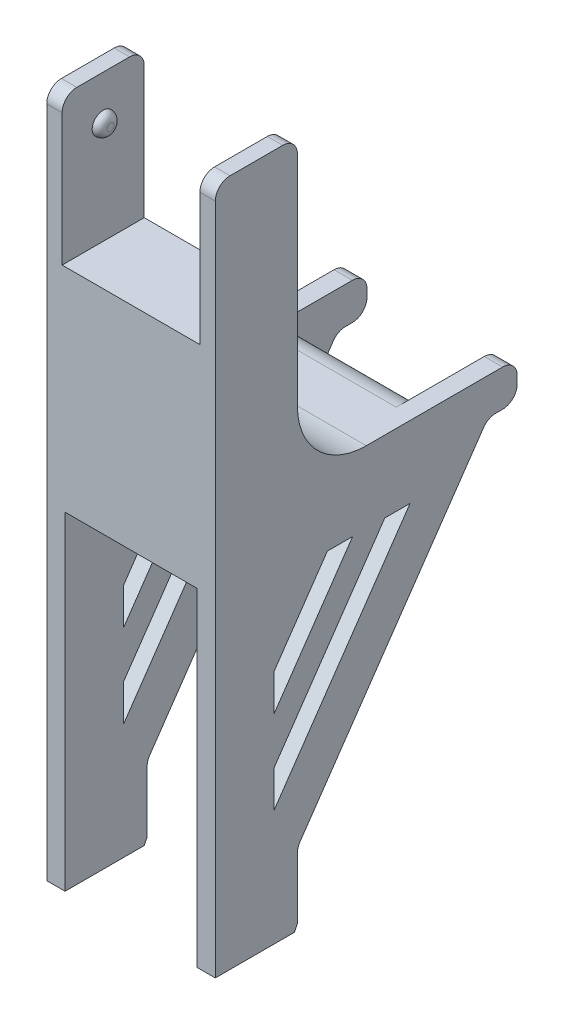
SolidWorks part; units mm, degrees
ref_plane "Front Plane" through (0, 0, 0) normal (0, 0, 1) x (1, 0, 0)
ref_plane "Top Plane" through (0, 0, 0) normal (0, 1, 0) x (1, 0, 0)
ref_plane "Right Plane" through (0, 0, 0) normal (1, 0, 0) x (0, 0, -1)
sketch "Szkic1" plane through (0, 0, 0) normal (1, 0, 0) x (0, 0, -1)
  line L2 (0, 0) -> (-10.3, 0)
  line L5 (-15, 4.7) -> (-15, 20.6)
  line L6 (-15, 20.6) -> (-20.6, 20.6)
  line L7 (-20.6, 20.6) -> (-20.6, -21.4)
  line L8 (0, 0) -> (0, -2.5)
  line L9 (0, -2.5) -> (-2, -2.5)
  line L10 (-2, -2.5) -> (-15, -21.4)
  line L11 (-15, -21.4) -> (-15, -25.9)
  line L13 (-20.6, -25.9) -> (-20.6, -21.4)
  line L17 (-20.6, -26.3) -> (-15.2, -26.3)
  line L18 (-15.2, -26.3) -> (-15, -25.9)
  line L19 (-20.6, -26.3) -> (-20.6, -25.9)
  arc A0 (-15, 4.7) -> (-10.3, 0) centre (-10.3, 4.7) ccw
  point P15 (-10.3, 4.7)
  dimension "D5" = 2.5
  dimension "D7" = 4.7
  dimension "D1" = 42
  dimension "D2" = 20.6
  dimension "D3" = 15.9
  dimension "D4" = 5.6
  dimension "D6" = 2
  dimension "D8" = 18.9
  dimension "D9" = 4.5
  dimension "D10" = 0.4
  dimension "D11" = 4.5
  dimension "D12" = 0.2
extrude "Dodanie-wyciągnięcie1" add sketch "Szkic1" along normal blind 11.5
ref_plane "Płaszczyzna dolna" through (0, 0, 20.6) normal (0, 0, 1) x (1, 0, 0)
sketch "Szkic2" plane through (0, 0, 20.6) normal (0, 0, 1) x (1, 0, 0)
  line L0 (5.75, 20.6) -> (5.75, -25.9) construction
  line L1 (11.5, 20.6) -> (0, 20.6) construction
  line L4 (10.45, 10.6) -> (1.05, 10.6)
  line L5 (10.45, 10.6) -> (10.45, 20.6)
  line L6 (10.45, 20.6) -> (1.05, 20.6)
  line L7 (1.05, 10.6) -> (1.05, 20.6)
  line L8 (10.45, 10.6) -> (1.05, 20.6) construction
  line L9 (10.45, 20.6) -> (1.05, 10.6) construction
  line L10 (10.25, -3.9) -> (1.25, -3.9)
  line L11 (10.25, -3.9) -> (10.25, -28.2703)
  line L12 (10.25, -28.2703) -> (1.25, -28.2703)
  line L13 (1.25, -3.9) -> (1.25, -28.2703)
  line L14 (10.25, -3.9) -> (1.25, -28.2703) construction
  line L15 (10.25, -28.2703) -> (1.25, -3.9) construction
  point P6 (5.75, 15.6)
  point P11 (5.75, -14.9)
  dimension "D1" = 9.4
  dimension "D2" = 10
  dimension "D3" = 9
  dimension "D4" = 11
extrude "Wytnij-wyciągnięcie1" cut sketch "Szkic2" against normal through all
ref_plane "Płaszczyzna boczna" through (11.5, 0, 0) normal (1, 0, 0) x (0, 0, -1)
sketch "Szkic3" plane through (11.5, 0, 0) normal (1, 0, 0) x (0, 0, -1)
  line L0 (-16.6, -12.7056) -> (-16.6, -10.1985)
  line L1 (-16.6, -10.1985) -> (-12.9555, -4.9)
  line L2 (-12.9555, -4.9) -> (-11.2311, -4.9)
  line L3 (-11.2311, -4.9) -> (-16.6, -12.7056)
  line L4 (-16.6, -15.8972) -> (-16.6, -18.4043)
  line L5 (-16.6, -18.4043) -> (-7.3113, -4.9)
  line L6 (-7.3113, -4.9) -> (-9.0358, -4.9)
  line L7 (-9.0358, -4.9) -> (-16.6, -15.8972)
  line L8 (-15, -21.4) -> (-2, -2.5) construction
  line L10 (-20.6, 6.325) -> (-20.6, -6.325) construction
  dimension "D1" = 4
  dimension "D2" = 21
extrude "Wytnij-wyciągnięcie2" cut sketch "Szkic3" against normal through all both and the other way through all
ref_plane "Płaszczyzna3" through (0, 0, 0) normal (0, 1, 0) x (1, 0, 0)
sketch "Szkic4" plane through (0, 0, 0) normal (0, 1, 0) x (1, 0, 0)
  line L0 (5.75, -5) -> (5.75, 0) construction
  line L2 (11.5, 0) -> (0, 0) construction
  line L4 (1.25, -5) -> (10.25, -5)
  line L5 (1.25, -5) -> (1.25, 0)
  line L6 (1.25, 0) -> (10.25, 0)
  line L7 (10.25, -5) -> (10.25, 0)
  line L8 (1.25, -5) -> (10.25, 0) construction
  line L9 (1.25, 0) -> (10.25, -5) construction
  point P6 (5.75, -2.5)
  dimension "D1" = 9
  dimension "D2" = 5
extrude "Wytnij-wyciągnięcie3" cut sketch "Szkic4" against normal blind 10
fillet "Zaokrąglenie1" radius 2 2 edges at (5.75, -3.9, 5) (5.75, 0, 5)
fillet "Zaokrąglenie2" radius 1 12 edges at (0.625, 0, 0) (0.625, -2.5, 0) (10.875, -2.5, 0) (10.875, 0, 0) (10.975, 20.6, 20.6) (10.975, 20.6, 15) (0.525, 20.6, 20.6) (0.525, 20.6, 15) (0.625, -2.5, 2) (10.875, -2.5, 2) (0.625, -21.4, 15) (10.875, -21.4, 15)
ref_plane "Płaszczyzna4" through (10.45, 0, 0) normal (-1, 0, 0) x (0, 0, 1)
sketch "Szkic5" plane through (10.45, 0, 0) normal (-1, 0, 0) x (0, 0, 1)
  line L3 (17.8, 20.6) -> (17.8, 10.6) construction
  line L4 (16, 20.6) -> (19.6, 20.6) construction
  line L5 (15, 10.6) -> (20.6, 10.6) construction
  circle A0 centre (17.8, 17.6) radius 0.75
  dimension "D1" = 1.5
  dimension "D2" = 3
extrude "Dodanie-wyciągnięcie2" add sketch "Szkic5" along normal blind 0.5
fillet "Zaokrąglenie3" radius 0.5 1 edges at (9.95, 16.85, 17.8)
ref_plane "Płaszczyzna5" through (5.75, 0, 0) normal (1, 0, 0) x (0, 0, -1)
mirror "Lustro2" about plane through (5.75, 0, 0) normal (1, 0, 0) of bodies 113 115
